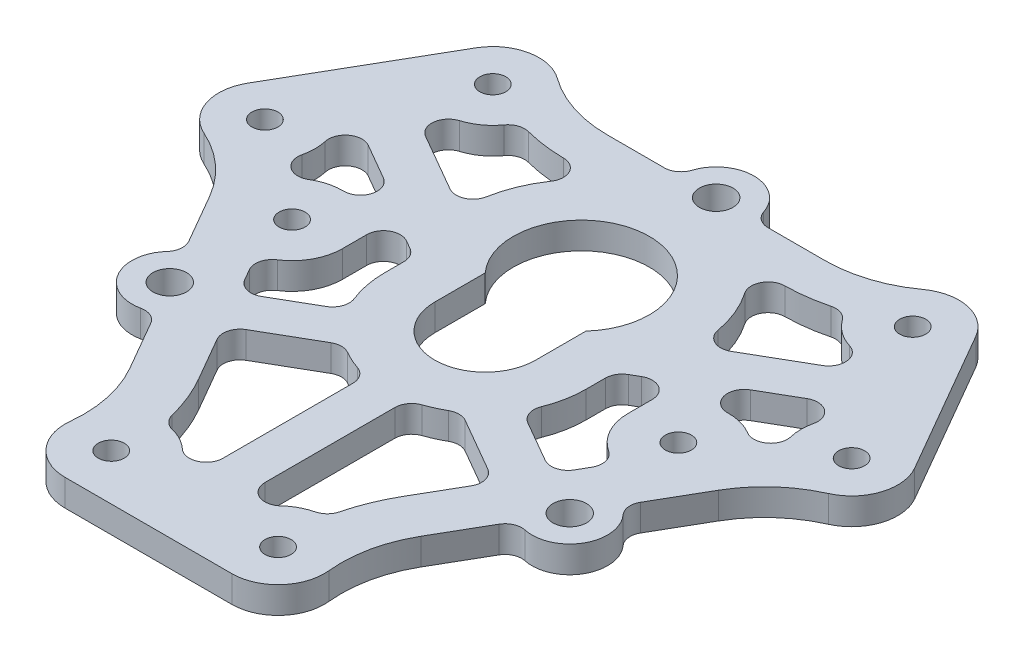
SolidWorks part; units mm, degrees
material "5052-H32"
ref_plane "Front Plane" through (0, 0, 0) normal (0, 0, 1) x (1, 0, 0)
ref_plane "Top Plane" through (0, 0, 0) normal (0, 1, 0) x (1, 0, 0)
ref_plane "Right Plane" through (0, 0, 0) normal (1, 0, 0) x (0, 0, -1)
sketch "Sketch1" plane through (0, 0, 0) normal (0, 1, 0) x (1, 0, 0)
  line L0 (0, 0) -> (0, 36) construction
  line L1 (-12.9662, 27.5) -> (12.9662, 27.5)
  line L2 (30.2988, -2.5209) -> (17.3326, -24.9791)
  line L3 (-25, 25.9037) -> (25, 25.9037) construction
  line L4 (-17.3326, -24.9791) -> (-30.2988, -2.5209)
  line L5 (29.7631, 28.6537) -> (39.6964, 11.4488)
  line L6 (9.9332, -40.1025) -> (-9.9332, -40.1025)
  line L7 (-29.7631, 28.6537) -> (-39.6964, 11.4488)
  line L8 (-6, 0) -> (-6, 6)
  line L9 (6, 0) -> (6, 6)
  circle A0 centre (0, 0) radius 6
  circle A1 centre (0, 0) radius 36 construction
  circle A2 centre (-25, 25.9037) radius 1.55
  circle A3 centre (25, 25.9037) radius 1.55
  arc A4 (-21.7714, 30.3563) -> (-29.7631, 28.6537) centre (-25, 25.9037) ccw
  arc A5 (29.7631, 28.6537) -> (21.7714, 30.3563) centre (25, 25.9037) ccw
  arc A6 (-21.7714, 30.3563) -> (-12.9662, 27.5) centre (-12.9662, 42.5) ccw
  arc A7 (12.9662, 27.5) -> (21.7714, 30.3563) centre (12.9662, 42.5) ccw
  arc A8 (37.1751, 3.6764) -> (39.6964, 11.4488) centre (34.9332, 8.6988) ccw
  circle A9 centre (34.9332, 8.6988) radius 1.55
  arc A10 (37.1751, 3.6764) -> (30.2988, -2.5209) centre (43.2892, -10.0209) ccw
  arc A11 (17.3326, -24.9791) -> (15.4037, -34.0328) centre (30.323, -32.4791) ccw
  arc A12 (9.9332, -40.1025) -> (15.4037, -34.0328) centre (9.9332, -34.6025) ccw
  arc A13 (-15.4037, -34.0328) -> (-9.9332, -40.1025) centre (-9.9332, -34.6025) ccw
  circle A14 centre (-9.9332, -34.6025) radius 1.55
  arc A15 (-15.4037, -34.0328) -> (-17.3326, -24.9791) centre (-30.323, -32.4791) ccw
  arc A16 (-30.2988, -2.5209) -> (-37.1751, 3.6764) centre (-43.2892, -10.0209) ccw
  arc A17 (-39.6964, 11.4488) -> (-37.1751, 3.6764) centre (-34.9332, 8.6988) ccw
  circle A18 centre (9.9332, -34.6025) radius 1.55
  circle A19 centre (-34.9332, 8.6988) radius 1.55
  arc A20 (6, 6) -> (-6, 6) centre (0, 11.4415) ccw
  circle A21 centre (0, 0) radius 8.1 construction
  circle A22 centre (-23, 0) radius 1.55
  circle A23 centre (23, 0) radius 1.55
  point P9 (0, 0)
  point P11 (0, 27.5)
  point P43 (0, 0)
  dimension "D1" = 12
  dimension "D2" = 72
  dimension "D4" = 3.1
  dimension "D5" = 11
  dimension "D6" = 15
  dimension "D9" = 16.2
  dimension "D3" = 50
  dimension "D8" = 27.5
  dimension "D10" = 6
  dimension "D11" = 23
  dimension "D7" = 3
extrude "Boss-Extrude1" add sketch "Sketch1" along normal blind 3.175 contours L7 A17 A16 L4 A15 A13 L6 A12 A11 L2 A10 A8 L5 A5 A7 L1 A6 A4 A20 L9 A0 L8 A19 A18 A2 A3 A9 A14 region at (0, 0, -26.4205)
sketch "Sketch6" plane through (0, 3.175, 0) normal (0, 1, 0) x (1, 0, 0)
  line L0 (-12.9662, 27.5) -> (12.9662, 27.5) construction
  line L1 (2, 27.5) -> (6.1847, 27.5)
  line L2 (22.8157, -15.4821) -> (20.7234, -19.1061)
  line L3 (-6.1847, 27.5) -> (-2, 27.5)
  line L4 (26.908, -8.3939) -> (24.8157, -12.0179)
  line L5 (-24.8157, -12.0179) -> (-26.908, -8.3939)
  line L6 (-20.7234, -19.1061) -> (-22.8157, -15.4821)
  circle A0 centre (0, 27.5) radius 2
  arc A1 (4.2817, 28.8846) -> (-4.2817, 28.8846) centre (0, 27.5) ccw
  arc A2 (-6.1847, 27.5) -> (-4.2817, 28.8846) centre (-6.1847, 29.5) ccw
  arc A3 (6.1847, 27.5) -> (4.2817, 28.8846) centre (6.1847, 29.5) cw
  arc A4 (20.7234, -19.1061) -> (22.874, -18.1504) centre (22.4554, -20.1061) cw
  arc A5 (22.874, -18.1504) -> (27.1557, -10.7343) centre (23.8157, -13.75) ccw
  arc A6 (26.908, -8.3939) -> (27.1557, -10.7343) centre (28.6401, -9.3939) ccw
  circle A7 centre (23.8157, -13.75) radius 2
  arc A8 (-26.908, -8.3939) -> (-27.1557, -10.7343) centre (-28.6401, -9.3939) cw
  arc A9 (-27.1557, -10.7343) -> (-22.874, -18.1504) centre (-23.8157, -13.75) ccw
  arc A10 (-20.7234, -19.1061) -> (-22.874, -18.1504) centre (-22.4554, -20.1061) ccw
  circle A11 centre (-23.8157, -13.75) radius 2
  point P35 (0, 0)
  line M4 (-30.2988, -2.5209) -> (-17.3326, -24.9791)
  line M10 (17.3326, -24.9791) -> (30.2988, -2.5209)
  line M16 (12.9662, 27.5) -> (-12.9662, 27.5)
  dimension "D1" = 4
  dimension "D2" = 9
  dimension "D3" = 2
  dimension "D4" = 3
extrude "Boss-Extrude2" add sketch "Sketch6" against normal up to surface (3.175 mm away) contours A3 A1 A2 A0 M16 | A11 A8 A9 A10 M4 | A7 A4 A5 A6 M10 region at (0, 3.175, -29.6006) region at (25.6348, 3.175, 14.8003) region at (-25.6348, 3.175, 14.8003) up to face at (0, 0, 0)
extrude "Cut-Extrude1" cut sketch "Sketch6<3>" against normal up to surface (3.175 mm away) contours A0 | A7 | A11 up to face at (0, 0, 0)
sketch "Sketch6<3>" plane through (0, 3.175, 0) normal (0, 1, 0) x (1, 0, 0) same geometry as "Sketch6"
sketch "Sketch8" plane through (0, 3.175, 0) normal (0, 1, 0) x (1, 0, 0)
  line L0 (-34.7298, 20.0512) -> (0, 0) construction
  line L1 (-29.7631, 28.6537) -> (-39.6964, 11.4488) construction
  line L2 (0, 0) -> (34.7298, 20.0512) construction
  line L3 (29.7631, 28.6537) -> (39.6964, 11.4488) construction
  line L4 (0, 0) -> (0, -40.1025) construction
  line L5 (9.9332, -40.1025) -> (-9.9332, -40.1025) construction
  line L6 (-23.6313, 16.5303) -> (-16.745, 12.5545)
  line L7 (0, 0) -> (0, 11.4415) construction
  line L8 (26.1313, 12.2002) -> (21.8541, 9.7307)
  line L9 (-14, 4.6188) -> (-13, 4.0415)
  line L10 (2.5, -13.2571) -> (2.5, -28.7305)
  line L11 (9.9332, -34.1025) -> (-9.9332, -34.1025)
  line L12 (-0.0006, 2.8871) -> (0, 2.8868)
  line L13 (-33.4798, 22.2163) -> (1.25, 2.1651) construction
  line L14 (23.6313, 16.5303) -> (16.745, 12.5545)
  line L15 (-24.1608, -13.9492) -> (0, 0) construction
  line L16 (-17, 0) -> (-17, 2.8868)
  line L17 (-12, 0) -> (-12, 6)
  line L18 (-12, 0) -> (-12, 2.3094)
  line L19 (-19.6195, -9.0179) -> (-20.375, -7.7094)
  line L20 (9.9332, -34.1025) -> (0, -34.1025)
  line L21 (-16.8875, -9.75) -> (-12, -6.9282)
  line L22 (12.1364, -21.9791) -> (15.1195, -16.8122)
  line L23 (-14.3875, -14.0801) -> (-8, -10.3923)
  line L24 (14.3875, -14.0801) -> (8, -10.3923)
  line L25 (12, 0) -> (12, 2.3094)
  line L26 (-12.1364, -21.9791) -> (-15.5272, -16.1061)
  line L27 (-12.1364, -21.9791) -> (-15.1195, -16.8122)
  line L28 (-36.2298, 17.4532) -> (-1.5, -2.5981) construction
  line L29 (-21.6608, -18.2794) -> (2.5, -4.3301) construction
  line L30 (-2.5, -13.2571) -> (-2.5, -28.7305)
  line L31 (16.8875, -9.75) -> (12, -6.9282)
  line L32 (19.6195, -9.0179) -> (20.375, -7.7094)
  line L33 (17, 0) -> (17, 2.8868)
  line L34 (14, 4.6188) -> (13, 4.0415)
  line L35 (-26.1313, 12.2002) -> (-21.8541, 9.7307)
  line L36 (-35.9798, 17.8862) -> (-1.25, -2.1651) construction
  circle A0 centre (-25, 25.9037) radius 1.55 construction
  arc A1 (-11.5395, 19.3687) -> (-13.7769, 13.9309) centre (0, 11.4415) ccw
  arc A2 (-16.745, 12.5545) -> (-13.7769, 13.9309) centre (-15.745, 14.2865) ccw
  arc A3 (-11.5395, 19.3687) -> (-13.1678, 22.501) centre (-13.188, 20.5011) ccw
  arc A4 (-18.0149, 23.1477) -> (-20.1399, 22.3853) centre (-18.5198, 21.2125) ccw
  arc A5 (-23.6313, 16.5303) -> (-23.2235, 20.1727) centre (-22.6313, 18.2624) cw
  arc A6 (6, 6) -> (-6, 6) centre (0, 11.4415) ccw construction
  arc A7 (11.5395, 19.3687) -> (13.7769, 13.9309) centre (0, 11.4415) cw
  arc A8 (16.745, 12.5545) -> (13.7769, 13.9309) centre (15.745, 14.2865) cw
  arc A9 (23.6313, 16.5303) -> (23.2235, 20.1727) centre (22.6313, 18.2624) ccw
  arc A10 (23.2235, 20.1727) -> (20.1399, 22.3853) centre (25, 25.9037) cw
  arc A11 (-23.2235, 20.1727) -> (-20.1399, 22.3853) centre (-25, 25.9037) ccw
  arc A12 (18.0149, 23.1477) -> (20.1399, 22.3853) centre (18.5198, 21.2125) cw
  arc A13 (-24.7065, 26.3085) -> (-12.9662, 22.5) centre (-12.9662, 42.5) ccw
  arc A14 (-18.0149, 23.1477) -> (-13.1678, 22.501) centre (-12.9662, 42.5) ccw
  arc A15 (18.0149, 23.1477) -> (13.1678, 22.501) centre (12.9662, 42.5) cw
  arc A16 (11.5395, 19.3687) -> (13.1678, 22.501) centre (13.188, 20.5011) cw
  arc A17 (-19.7322, -5.0321) -> (-17, 0) centre (-23, 0) ccw
  arc A18 (-6, -10.3923) -> (-3.8571, -11.3632) centre (0, 0) ccw
  arc A19 (-5.8583, -30.1985) -> (-8.5034, -28.7753) centre (-9.9332, -34.6025) ccw
  arc A20 (-8.5034, -28.7753) -> (-9.9656, -27.3239) centre (-8.0268, -26.833) cw
  arc A21 (-15.1195, -16.8122) -> (-14.3875, -14.0801) centre (-13.3875, -15.8122) cw
  arc A22 (-12, 0) -> (12, 0) centre (0, 0) ccw
  arc A23 (-12, 0) -> (-11.1429, -4.4538) centre (0, 0) ccw
  arc A24 (-8, -10.3923) -> (-6, -10.3923) centre (-7, -12.1244) cw
  arc A25 (-3.8571, -11.3632) -> (-2.5, -13.2571) centre (-4.5, -13.2571) cw
  arc A26 (-13, 4.0415) -> (-12, 2.3094) centre (-14, 2.3094) cw
  arc A27 (-9.4359, -34.6543) -> (-12.1364, -21.9791) centre (-30.323, -32.4791) ccw
  arc A28 (-9.9656, -27.3239) -> (-12.1364, -21.9791) centre (-30.323, -32.4791) ccw
  arc A29 (-11.1429, -4.4538) -> (-12, -6.9282) centre (-13, -5.1962) cw
  arc A30 (-16.8875, -9.75) -> (-19.6195, -9.0179) centre (-17.8875, -8.0179) cw
  arc A31 (-20.375, -7.7094) -> (-19.7322, -5.0321) centre (-18.643, -6.7094) cw
  arc A32 (-17, 2.8868) -> (-14, 4.6188) centre (-15, 2.8868) cw
  arc A33 (-5.8583, -30.1985) -> (-2.5, -28.7305) centre (-4.5, -28.7305) ccw
  arc A34 (5.8583, -30.1985) -> (2.5, -28.7305) centre (4.5, -28.7305) cw
  arc A35 (5.8583, -30.1985) -> (8.5034, -28.7753) centre (9.9332, -34.6025) cw
  arc A36 (8.5034, -28.7753) -> (9.9656, -27.3239) centre (8.0268, -26.833) ccw
  arc A37 (9.9656, -27.3239) -> (12.1364, -21.9791) centre (30.323, -32.4791) cw
  arc A38 (15.1195, -16.8122) -> (14.3875, -14.0801) centre (13.3875, -15.8122) ccw
  arc A39 (8, -10.3923) -> (6, -10.3923) centre (7, -12.1244) ccw
  arc A40 (6, -10.3923) -> (3.8571, -11.3632) centre (0, 0) cw
  arc A41 (3.8571, -11.3632) -> (2.5, -13.2571) centre (4.5, -13.2571) ccw
  arc A42 (12, 0) -> (11.1429, -4.4538) centre (0, 0) cw
  arc A43 (11.1429, -4.4538) -> (12, -6.9282) centre (13, -5.1962) ccw
  arc A44 (16.8875, -9.75) -> (19.6195, -9.0179) centre (17.8875, -8.0179) ccw
  arc A45 (20.375, -7.7094) -> (19.7322, -5.0321) centre (18.643, -6.7094) ccw
  arc A46 (19.7322, -5.0321) -> (17, 0) centre (23, 0) cw
  arc A47 (17, 2.8868) -> (14, 4.6188) centre (15, 2.8868) ccw
  arc A48 (13, 4.0415) -> (12, 2.3094) centre (14, 2.3094) ccw
  arc A49 (-29.0978, 7.303) -> (-29.0818, 10.0258) centre (-34.9332, 8.6988) ccw
  arc A50 (-22.8906, 5.999) -> (-26.1145, 5.1283) centre (-23, 0) ccw
  arc A51 (22.8906, 5.999) -> (26.1145, 5.1283) centre (23, 0) cw
  arc A52 (-22.8906, 5.999) -> (-21.8541, 9.7307) centre (-22.8541, 7.9987) ccw
  arc A53 (29.0978, 7.303) -> (26.1145, 5.1283) centre (27.1527, 6.8378) cw
  arc A54 (29.0978, 7.303) -> (29.0818, 10.0258) centre (34.9332, 8.6988) cw
  arc A55 (-26.1313, 12.2002) -> (-29.0818, 10.0258) centre (-27.1313, 10.4681) ccw
  arc A56 (-19.7322, -5.0321) -> (-17, 0) centre (-23, 0) ccw
  arc A57 (-29.0978, 7.303) -> (-26.1145, 5.1283) centre (-27.1527, 6.8378) ccw
  arc A58 (26.1313, 12.2002) -> (29.0818, 10.0258) centre (27.1313, 10.4681) cw
  arc A59 (22.8906, 5.999) -> (21.8541, 9.7307) centre (22.8541, 7.9987) cw
  point P16 (-23.8157, -13.75)
  point P43 (-7.5046, 23.2602)
  point P90 (-6.9472, -9.7845)
  point P93 (-2.5, -11.7367)
  point P100 (-18.6195, -10.75)
  dimension "D3" = 2
  dimension "D5" = 14
  dimension "D6" = 6
  dimension "D8" = 6
  dimension "D13" = 2
  dimension "D14" = 4
  dimension "D17" = 4
  dimension "D11" = 6
  dimension "D12" = 2.5
  dimension "D1" = 2.5
  dimension "D2" = 3
  dimension "D4" = 5
  dimension "D7" = 6
  dimension "D9" = 5
  dimension "D10" = 6
  dimension "D16" = 2.5
extrude "Cut-Extrude2" cut sketch "Sketch8" against normal up to surface (3.175 mm away) contours A14 A4 A11 A5 L6 A2 A1 A3 | A49 A57 A50 A52 L35 A55 | A32 L16 A17 A31 L19 A30 L21 A29 A23 L18 A26 L9 | A19 A33 L30 A25 A18 A24 L23 A21 L27 A28 A20 | A40 A41 L10 A34 A35 A36 A37 L22 A38 L24 A39 | L34 A48 L25 A42 A43 L31 A44 L32 A45 A46 L33 A47 | A59 A51 A53 A54 A58 L8 | A16 A7 A8 L14 A9 A10 A12 A15 region at (-17.5041, 3.175, -18.2167) region at (25.5847, 3.175, -8.5058) region at (15.3613, 3.175, 3.1579) region at (7.5513, 3.175, 19.6539) region at (-7.5513, 3.175, 19.6539) region at (-15.3613, 3.175, 3.1579) region at (17.5041, 3.175, -18.2167) region at (-25.5847, 3.175, -8.5058) up to face at (0, 0, 0)
